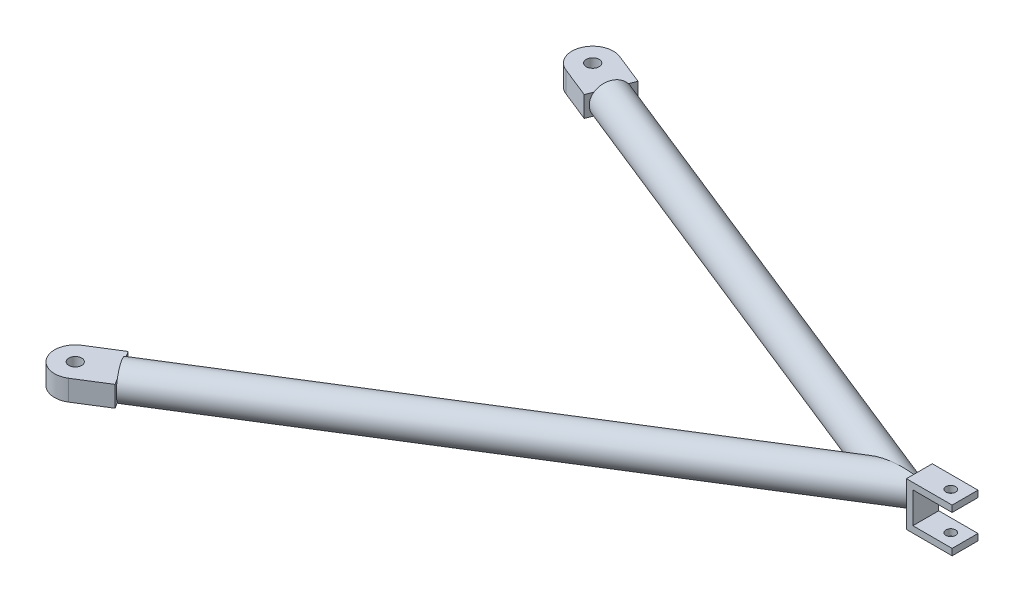
SolidWorks part; units mm, degrees
ref_plane "Front Plane" through (0, 0, 0) normal (0, 0, 1) x (1, 0, 0)
ref_plane "Top Plane" through (0, 0, 0) normal (0, 1, 0) x (1, 0, 0)
ref_plane "Right Plane" through (0, 0, 0) normal (1, 0, 0) x (0, 0, -1)
sketch "Sketch1" plane through (0, 0, 0) normal (0, 1, 0) x (1, 0, 0)
  line L0 (0, 0) -> (-247.6207, 99.06)
  line L1 (0, 0) -> (-247.6207, -154.94)
  line L2 (-247.6207, 99.06) -> (-247.6207, -154.94) construction
  dimension "D1" = 266.7
  dimension "D2" = 292.1
  dimension "D3" = 254
ref_plane "Plane1" through (-247.6207, 0, 154.94) normal (-0.8477, 0, 0.5304) x (0.5304, 0, 0.8477)
sketch "Sketch2" plane through (-247.6207, 0, 154.94) normal (-0.8477, 0, 0.5304) x (0.5304, 0, 0.8477)
  circle A0 centre (0, 0) radius 8.255
  dimension "D1" = 16.51
sweep "Sweep1" add profiles "Sketch2" path "Sketch1"
sketch "Sketch3" plane through (0, 0, 0) normal (0, 0, 1) x (1, 0, 0)
  line L0 (34.2567, -10.795) -> (11.811, -10.795)
  line L1 (11.811, -10.795) -> (11.811, 10.795)
  line L2 (11.811, 10.795) -> (34.2567, 10.795)
  line L3 (34.2567, 10.795) -> (34.2567, 7.62)
  line L4 (34.2567, 7.62) -> (14.986, 7.62)
  line L5 (14.986, 7.62) -> (14.986, -7.62)
  line L6 (14.986, -7.62) -> (34.2567, -7.62)
  line L7 (34.2567, -7.62) -> (34.2567, -10.795)
  line L8 (-18.161, 0) -> (18.161, 0) construction
  ellipse E0 centre (0, 0) end of major axis (18.161, 0) minor radius 8.255 construction
  ellipse E1 centre (0, 0) end of major axis (18.161, 0) minor radius 8.255 construction
  point P21 (11.811, 0)
  dimension "D1" = 3.175
  dimension "D2" = 15.24
  dimension "D3" = 3.175
  dimension "D4" = 6.35
extrude "Boss-Extrude1" add sketch "Sketch3" along normal blind 6.35 and the other way blind 6.35
sketch "Sketch4" plane through (-247.6207, 0, 154.94) normal (-0.8477, 0, 0.5304) x (0.5304, 0, 0.8477)
  line L1 (-10.16, 5.08) -> (10.16, 5.08)
  line L2 (-10.16, 5.08) -> (-10.16, -5.08)
  line L3 (-10.16, -5.08) -> (10.16, -5.08)
  line L4 (10.16, 5.08) -> (10.16, -5.08)
  line L5 (-10.16, 5.08) -> (10.16, -5.08) construction
  line L6 (-10.16, -5.08) -> (10.16, 5.08) construction
  point P0 (0, 0)
  dimension "D1" = 20.32
  dimension "D2" = 10.16
extrude "Boss-Extrude2" add sketch "Sketch4" along normal blind 10.16 and the other way blind 16.51
sketch "Sketch5" plane through (-247.6207, 0, -99.06) normal (-0.9285, 0, -0.3714) x (-0.3714, 0, 0.9285)
  line L1 (-10.16, 5.08) -> (10.16, 5.08)
  line L2 (-10.16, 5.08) -> (-10.16, -5.08)
  line L3 (-10.16, -5.08) -> (10.16, -5.08)
  line L4 (10.16, 5.08) -> (10.16, -5.08)
  line L5 (-10.16, 5.08) -> (10.16, -5.08) construction
  line L6 (-10.16, -5.08) -> (10.16, 5.08) construction
  point P0 (0, 0)
  dimension "D1" = 20.32
  dimension "D2" = 10.16
extrude "Boss-Extrude3" add sketch "Sketch5" along normal blind 10.16 and the other way blind 16.256
sketch "Sketch7" plane through (0, 5.08, 0) normal (0, 1, 0) x (1, 0, 0)
  line L8 (-236.3013, 83.5889) -> (-234.9444, 86.9807)
  line L9 (-234.9444, 86.9807) -> (-250.0375, 93.0187)
  line L10 (-250.0375, 93.0187) -> (-245.2039, 105.1013)
  line L11 (-245.2039, 105.1013) -> (-230.1108, 99.0634)
  line L12 (-230.1108, 99.0634) -> (-228.7539, 102.4552)
  line L13 (-228.7539, 102.4552) -> (-253.2801, 112.2669)
  line L14 (-253.2801, 112.2669) -> (-260.8276, 93.4005)
  line L15 (-260.8276, 93.4005) -> (-236.3013, 83.5889)
  line L22 (-257.0539, 102.8337) -> (-260.8276, 93.4005)
  line L23 (-260.8276, 93.4005) -> (-251.3944, 89.6268)
  arc A0 (-257.0539, 102.8337) -> (-251.3944, 89.6268) centre (-247.6207, 99.06) ccw
  dimension "D1" = 0
extrude "Cut-Extrude1" cut sketch "Sketch7" against normal through all
ref_plane "Plane2" through (0, 0, 0) normal (-0.3714, 0, 0.9285) x (0.9285, 0, 0.3714)
mirror "Mirror1" about plane through (0, 0, 0) normal (-0.3714, 0, 0.9285) of "Cut-Extrude1"
sketch "Sketch9" plane through (0, 5.08, 0) normal (0, 1, 0) x (1, 0, 0)
  line L0 (-239.014, -137.5696) -> (-261.6228, -151.7163) construction
  line L1 (-228.2355, -154.7954) -> (-250.8444, -168.9421) construction
  line L2 (-250.8444, -168.9421) -> (-261.6228, -151.7163) construction
  line L3 (-242.2315, -163.5529) -> (-250.8444, -168.9421)
  line L4 (-250.8444, -168.9421) -> (-256.2336, -160.3292)
  arc A0 (-256.2336, -160.3292) -> (-242.2315, -163.5529) centre (-247.6207, -154.94) ccw
extrude "Cut-Extrude2" cut sketch "Sketch9" against normal through all
ref_plane "Plane3" through (0, 0, 0) normal (0.5304, 0, 0.8477) x (0.8477, 0, -0.5304)
mirror "Mirror2" about plane through (0, 0, 0) normal (0.5304, 0, 0.8477) of "Cut-Extrude2"
sketch "Sketch10" plane through (-247.6207, 0, 154.94) normal (-0.8477, 0, 0.5304) x (0.5304, 0, 0.8477)
  line L0 (6.5068, -5.08) -> (-6.5068, -5.08) construction
  line L1 (-6.5068, 5.08) -> (6.5068, 5.08) construction
  line L2 (6.5068, -5.08) -> (-6.5068, -5.08)
  line L3 (-6.5068, 5.08) -> (6.5068, 5.08)
  arc A0 (-6.5068, -5.08) -> (6.5068, -5.08) centre (0, 0) ccw construction
  arc A1 (6.5068, 5.08) -> (-6.5068, 5.08) centre (0, 0) ccw construction
  arc A2 (-6.5068, -5.08) -> (6.5068, -5.08) centre (0, 0) ccw
  arc A3 (6.5068, 5.08) -> (-6.5068, 5.08) centre (0, 0) ccw
extrude "Cut-Extrude3" cut sketch "Sketch10" against normal up to surface (16.51 mm away) up to face at (-228.9726, 0, 153.6175)
sketch "Sketch11" plane through (-247.6207, 0, -99.06) normal (-0.9285, 0, -0.3714) x (-0.3714, 0, 0.9285)
  line L0 (6.5068, -5.08) -> (-6.5068, -5.08) construction
  line L1 (-6.5068, 5.08) -> (6.5068, 5.08) construction
  line L2 (6.5068, -5.08) -> (-6.5068, -5.08)
  line L3 (-6.5068, 5.08) -> (6.5068, 5.08)
  arc A0 (-6.5068, -5.08) -> (6.5068, -5.08) centre (0, 0) ccw construction
  arc A1 (6.5068, 5.08) -> (-6.5068, 5.08) centre (0, 0) ccw construction
  arc A2 (-6.5068, -5.08) -> (6.5068, -5.08) centre (0, 0) ccw
  arc A3 (6.5068, 5.08) -> (-6.5068, 5.08) centre (0, 0) ccw
extrude "Cut-Extrude4" cut sketch "Sketch11" along direction (0.9285, 0, 0.3714) on the side against the normal up to surface (16.256 mm away) up to face at (-235.7852, 0, -84.879)
sketch "Sketch12" plane through (0, 0, 6.35) normal (0, 0, 1) x (1, 0, 0)
  line L1 (14.986, 4.6631) -> (14.986, -4.6631)
  line L2 (14.986, 4.6631) -> (14.986, -4.6631)
  ellipse E1 centre (0, 0) end of major axis (18.161, 0) minor radius 8.255 (14.986, -4.6631) -> (14.986, 4.6631) ccw
  ellipse E2 centre (0, 0) end of major axis (18.161, 0) minor radius 8.255 (14.986, -4.6631) -> (14.986, 4.6631) ccw
  dimension "D1" = 0
extrude "Cut-Extrude5" cut sketch "Sketch12" against normal through all
sketch "Sketch13" plane through (0, 5.08, 0) normal (0, 1, 0) x (1, 0, 0)
  point P0 (-247.6207, 99.06)
  point P1 (-247.6207, -154.94)
hole_wizard "E (0.25) Diameter Hole1" positions "3DSketch1" profile "Sketch14" hole size "E" standard "ANSI Inch"
sketch3d "3DSketch1"
  point P0 (-247.6207, 5.08, -99.06)
  point P3 (-247.6207, 5.08, 154.94)
sketch "Sketch14" plane through (-247.6207, 5.08, -99.06) normal (1, 0, 0) x (0, 0, 1)
  line L0 (0, 0) -> (0, 20.9577)
  line L1 (0, 20.9577) -> (3.175, 19.05)
  line L2 (3.175, 19.05) -> (3.175, 0)
  line L5 (3.175, 0) -> (0, 0)
  line L10 (0, 20.9577) -> (-3.175, 19.05) construction
  line L11 (0, -6.35) -> (0, 107.95) construction
  dimension "Hole Dia." = 6.35
  dimension "Hole Depth" = 19.05
  dimension "Drill Angle" = 118
hole_wizard "3/16 (0.1875) Diameter Hole1" positions "Sketch15" profile "Sketch16" hole size "3/16" standard "ANSI Inch" end condition through all
sketch "Sketch15" plane through (0, 10.795, 0) normal (0, 1, 0) x (1, 0, 0)
  line L0 (-11.8745, 0) -> (11.8745, 0) construction
  point P0 (27.2415, 0)
sketch "Sketch16" plane through (27.2415, 10.795, 0) normal (1, 0, 0) x (0, 0, 1)
  line L0 (0, 0) -> (0, 21.59)
  line L1 (0, 21.59) -> (2.3812, 21.59)
  line L2 (2.3812, 21.59) -> (2.3812, 0)
  line L5 (2.3812, 0) -> (0, 0)
  line L11 (0, -6.35) -> (0, 107.95) construction
  dimension "Thru Hole Dia." = 4.7625
  dimension "Thru Hole Depth" = 21.59
ref_point "Point1"
ref_point "Point2"
sketch3d "3DSketch2"
  line L0 (27.2415, 7.62, 0) -> (27.2415, -7.62, 0) construction
  circle A0 centre (27.2415, 7.62, 0) radius 2.3812 construction
  circle A1 centre (27.2415, -7.62, 0) radius 2.3812 construction
  circle A2 centre (27.2415, 7.62, 0) radius 2.3812 construction
  circle A3 centre (27.2415, -7.62, 0) radius 2.3812 construction
  point P2 (27.2415, 5.2388, 0)
  point P5 (27.2415, -5.2388, 0)
  point P7 (27.2415, 5.2388, 0)
  point P9 (27.2415, -5.2388, 0)
  point P10 (27.2415, 0, 0)
ref_point "JOINT"
